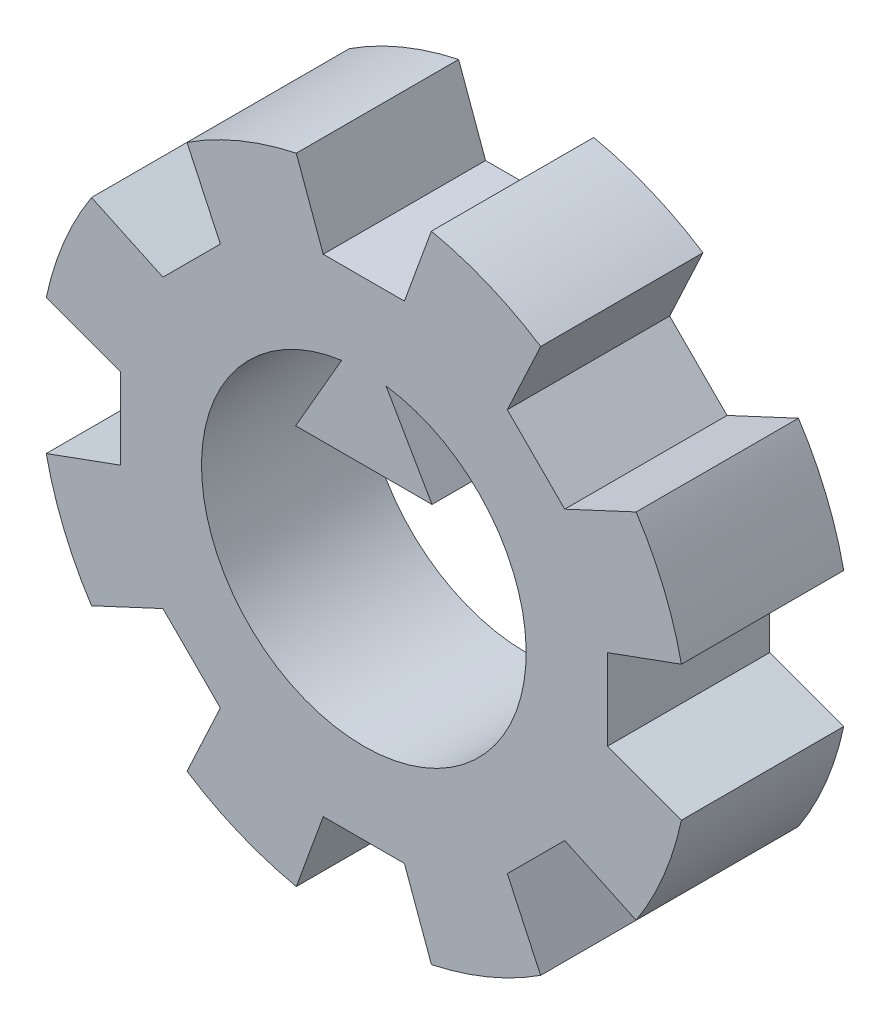
SolidWorks part; units mm, degrees
ref_plane "前视基准面" through (0, 0, 0) normal (0, 0, 1) x (1, 0, 0)
ref_plane "上视基准面" through (0, 0, 0) normal (0, 1, 0) x (1, 0, 0)
ref_plane "右视基准面" through (0, 0, 0) normal (1, 0, 0) x (0, 0, -1)
sketch "Sketch1" plane through (0, 0, 0) normal (0, 0, 1) x (1, 0, 0)
  line L0 (-0.0684, 0.4953) -> (-0.21, 0.25)
  line L1 (-0.21, 0.25) -> (0.21, 0.25)
  line L2 (0.21, 0.25) -> (0.0684, 0.4953)
  line L3 (0, 0) -> (0, 50000) construction
  line L4 (0.208, 0.9781) -> (0.125, 0.75)
  line L5 (0.125, 0.75) -> (-0.125, 0.75)
  line L6 (-0.125, 0.75) -> (-0.208, 0.9781)
  circle A0 centre (0, 0) radius 1
  arc A1 (-0.0684, 0.4953) -> (0.0684, 0.4953) centre (0, 0) ccw
  point P6 (0, 0)
  point P11 (0, 0.25)
  point P15 (0, 0.75)
  dimension "D1" = 2
  dimension "D2" = 1
  dimension "D3" = 0.42
  dimension "D4" = 30
  dimension "D5" = 30
  dimension "D6" = 0.25
  dimension "D7" = 0.25
  dimension "D8" = 20
  dimension "D9" = 20
  dimension "D10" = 0.75
extrude "Boss-Extrude2" add sketch "Sketch1" along normal blind 0.5 contours L3 A0 L4 L5 L1 L2 A1 | A0 L3 A1 L0 L1 L5 L6 | L3 L5 L4 A0 | L5 L3 A0 L6 region at (0.0625, 0.7219, 0) region at (-0.0845, 0.8819, 0) region at (0.0845, 0.8819, 0)
extrude "Cut-Extrude1" cut sketch "Sketch1<4>" against normal through all and the other way through all contours L3 L5 L4 A0 | L5 L3 A0 L6 region at (-0.0845, 0.8819, 0) region at (0.0845, 0.8819, 0)
sketch "Sketch1<4>" plane through (0, 0, 0) normal (0, 0, 1) x (1, 0, 0) same geometry as "Sketch1"
pattern_circular "CirPattern1" count 8 over 360 about axis through (0, 0, 0.5) along (0, 0, -1) of "Cut-Extrude1"
